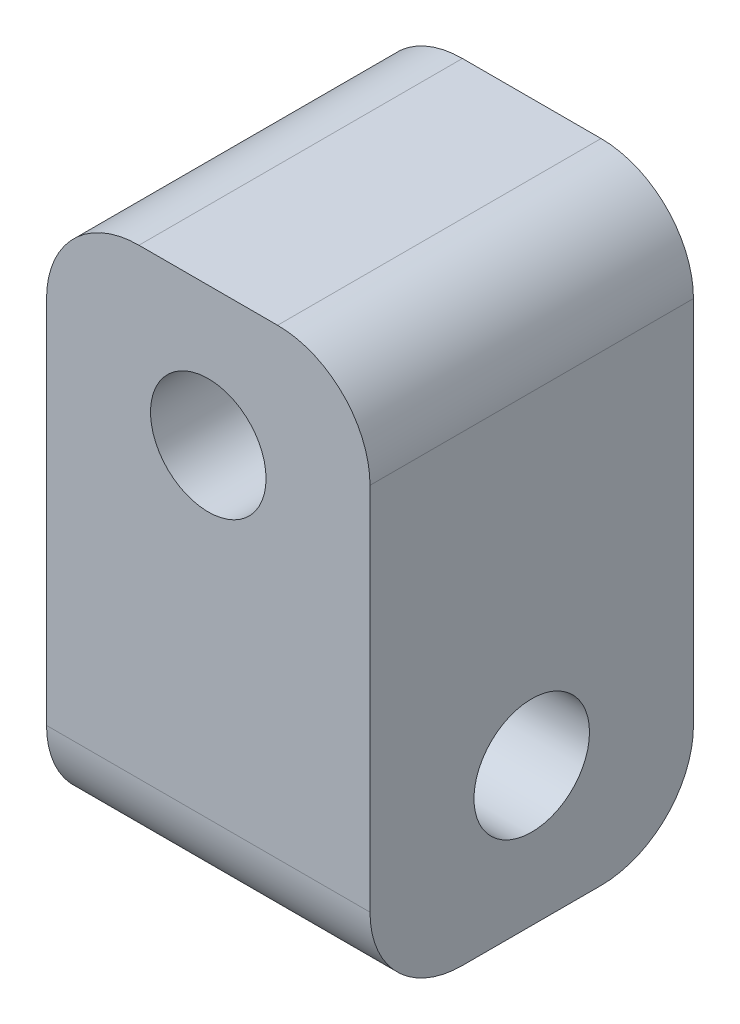
SolidWorks part; units mm, degrees
ref_plane "Front Plane" through (0, 0, 0) normal (0, 0, 1) x (1, 0, 0)
ref_plane "Top Plane" through (0, 0, 0) normal (0, 1, 0) x (1, 0, 0)
ref_plane "Right Plane" through (0, 0, 0) normal (1, 0, 0) x (0, 0, -1)
sketch "Sketch1" plane through (0, 0, 0) normal (0, 0, 1) x (1, 0, 0)
  line L1 (-15, 30.0007) -> (15, 30.0007)
  line L2 (35, 10.0007) -> (35, -29.9993)
  line L3 (35, -29.9993) -> (-35, -29.9993)
  line L5 (-35, -29.9993) -> (-35, 10.0007)
  circle A0 centre (0, 0) radius 12.5
  arc A1 (35, 10.0007) -> (15, 30.0007) centre (15, 10.0007) ccw
  arc A2 (-15, 30.0007) -> (-35, 10.0007) centre (-15, 10.0007) ccw
  point P11 (35, 30.0007)
  point P14 (-35, 30.0007)
  dimension "D3" = 20
  dimension "D5" = 25
  dimension "D1" = 35
  dimension "D2" = 60
  dimension "D4" = 70
extrude "Boss-Extrude1" add sketch "Sketch1" along normal blind 70
sketch "Sketch2" plane through (0, 0, 0) normal (1, 0, 0) x (0, 0, -1)
  line L0 (-70, -29.9993) -> (-70, -69.9993)
  line L1 (-50, -89.9993) -> (-20, -89.9993)
  line L2 (0, -69.9993) -> (0, -29.9993)
  line L5 (-70, -29.9993) -> (0, -29.9993)
  circle A0 centre (-35, -59.9993) radius 12.5
  arc A1 (0, -69.9993) -> (-20, -89.9993) centre (-20, -69.9993) cw
  arc A2 (-70, -69.9993) -> (-50, -89.9993) centre (-50, -69.9993) ccw
  point P12 (-70, -89.9993)
  dimension "D2" = 20
  dimension "D5" = 25
  dimension "D1" = 60
  dimension "D3" = 70
  dimension "D4" = 35
extrude "Boss-Extrude2" add sketch "Sketch2" along normal mid plane 70
